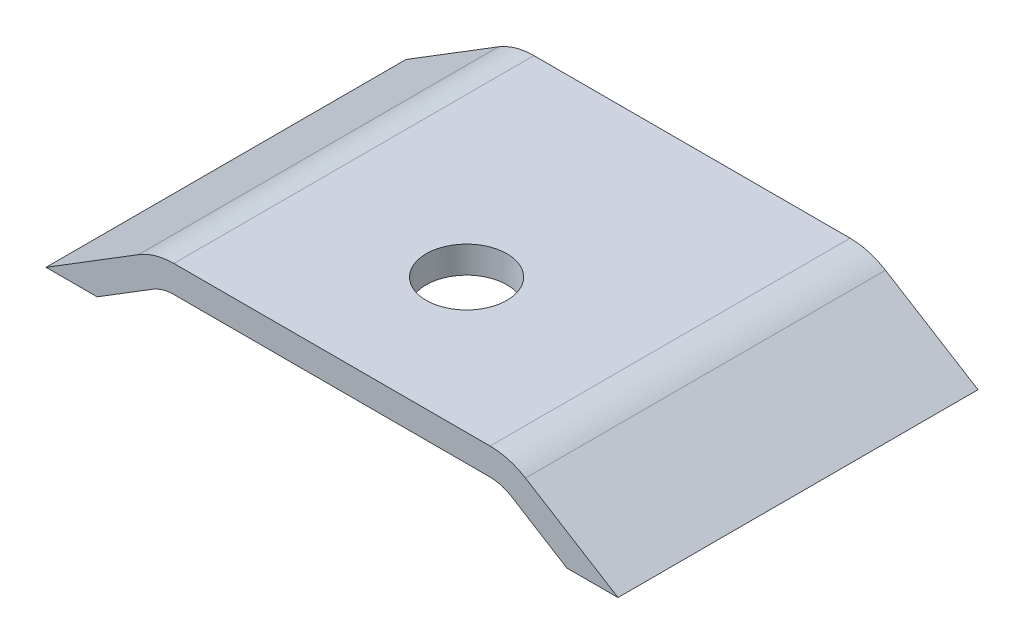
SolidWorks part; units mm, degrees
ref_plane "Front Plane" through (0, 0, 0) normal (0, 0, 1) x (1, 0, 0)
ref_plane "Top Plane" through (0, 0, 0) normal (0, 1, 0) x (1, 0, 0)
ref_plane "Right Plane" through (0, 0, 0) normal (1, 0, 0) x (0, 0, -1)
sketch "Sketch1" plane through (0, 0, 0) normal (0, 0, 1) x (1, 0, 0)
  line L0 (-53.975, -6.35) -> (-33.4494, 6.35)
  line L1 (53.975, -6.35) -> (-53.975, -6.35) construction
  line L2 (53.975, -6.35) -> (53.975, 6.35) construction
  line L3 (53.975, 6.35) -> (-53.975, 6.35) construction
  line L4 (-53.975, -6.35) -> (-53.975, 6.35) construction
  line L5 (53.975, -6.35) -> (-53.975, 6.35) construction
  line L6 (53.975, 6.35) -> (-53.975, -6.35) construction
  line L7 (-33.4494, 6.35) -> (33.4494, 6.35)
  line L8 (33.4494, 6.35) -> (53.975, -6.35)
  line L9 (53.975, -6.35) -> (-53.975, -6.35)
  point P0 (0, 0)
  dimension "D1" = 107.95
  dimension "D2" = 12.7
  dimension "D3" = 148.253
extrude "Boss-Extrude1" add sketch "Sketch1" along normal blind 67.945
fillet "Fillet1" radius 12.7 2 edges at (-33.4494, 6.35, 33.9725) (33.4494, 6.35, 33.9725)
sketch "Sketch3" plane through (0, 0, 67.945) normal (0, 0, 1) x (1, 0, 0)
  line L27 (-51.3021, -10.6699) -> (51.3021, -10.6699)
  line L30 (51.3021, -10.6699) -> (33.8475, 0.1299)
  line L31 (29.8381, 1.27) -> (-29.8381, 1.27)
  line L32 (-33.8475, 0.1299) -> (-51.3021, -10.6699)
  line L33 (51.3021, -10.6699) -> (33.8475, 0.1299)
  line L34 (29.8381, 1.27) -> (-29.8381, 1.27)
  line L35 (-33.8475, 0.1299) -> (-51.3021, -10.6699)
  arc A17 (33.8475, 0.1299) -> (29.8381, 1.27) centre (29.8381, -6.35) ccw
  arc A18 (-29.8381, 1.27) -> (-33.8475, 0.1299) centre (-29.8381, -6.35) ccw
  arc A19 (33.8475, 0.1299) -> (29.8381, 1.27) centre (29.8381, -6.35) ccw
  arc A20 (-29.8381, 1.27) -> (-33.8475, 0.1299) centre (-29.8381, -6.35) ccw
  dimension "D1" = 5.08
extrude "Cut-Extrude1" cut sketch "Sketch3" against normal up to next
ref_plane "Plane1" through (0, 0, 33.9725) normal (0, 0, -1) x (-1, 0, 0)
sketch "Sketch4" plane through (0, 0, 0) normal (0, 1, 0) x (1, 0, 0)
  circle A0 centre (-52.8588, -9.8061) radius 3.0953
sketch "Sketch5" plane through (0, 6.35, 0) normal (0, 1, 0) x (1, 0, 0)
  line L0 (29.8381, -67.945) -> (-29.8381, -67.945) construction
  circle A0 centre (0, -42.545) radius 7.62
  dimension "D1" = 15.24
  dimension "D2" = 25.4
extrude "Cut-Extrude2" cut sketch "Sketch5" against normal up to next
